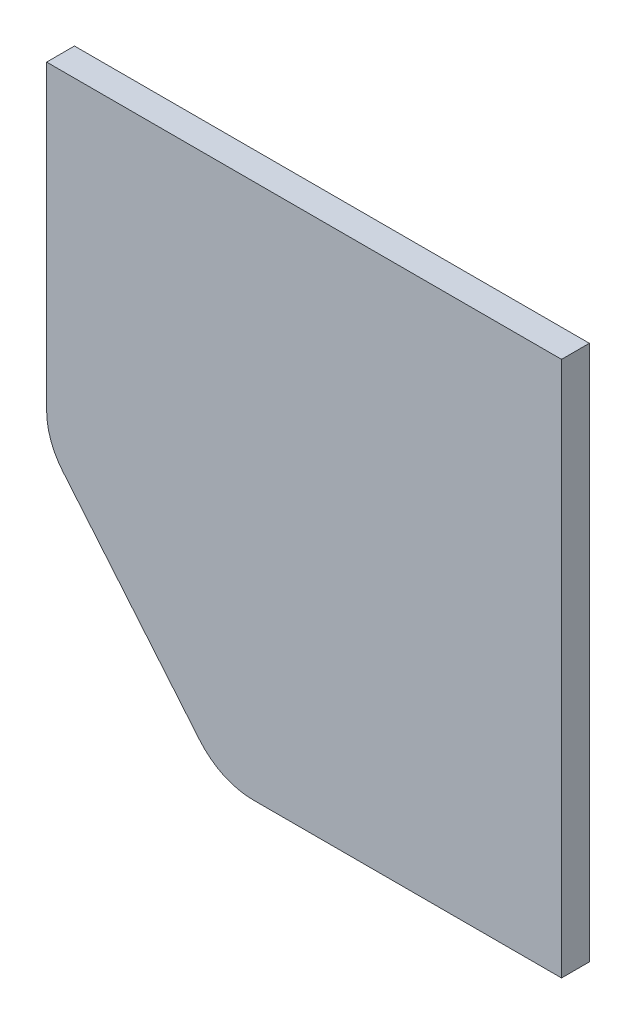
SolidWorks part; units mm, degrees
ref_plane "Plano frontal" through (0, 0, 0) normal (0, 0, 1) x (1, 0, 0)
ref_plane "Plano superior" through (0, 0, 0) normal (0, 1, 0) x (1, 0, 0)
ref_plane "Plano direito" through (0, 0, 0) normal (1, 0, 0) x (0, 0, -1)
sketch "Esboço1" plane through (0, 0, 0) normal (0, 0, 1) x (1, 0, 0)
  line L1 (-86.1657, 44.0263) -> (-12.1657, 44.0263)
  line L2 (-86.1657, 44.0263) -> (-86.1657, -32.9737)
  line L3 (-86.1657, -32.9737) -> (-12.1657, -32.9737)
  line L4 (-12.1657, 44.0263) -> (-12.1657, -32.9737)
  dimension "D1" = 77
  dimension "D2" = 74
extrude "Ressalto-extrusão1" add sketch "Esboço1" along normal blind 4
sketch "Esboço4" plane through (0, 0, 4) normal (0, 0, 1) x (1, 0, 0)
  line L0 (-61.1657, -32.9737) -> (-86.1657, -2.9737)
  line L1 (-86.1657, -32.9737) -> (-12.1657, -32.9737) construction
  line L2 (-86.1657, 44.0263) -> (-86.1657, -32.9737) construction
  dimension "D1" = 30
  dimension "D2" = 25
extrude "Corte-extrusão2" cut sketch "Esboço4" against normal through all and the other way through all
fillet "Filete2" radius 10 1 edges at (-86.1657, -2.9737, 2) type face fillet first side face at (-86.1657, 20.5263, 2) second side face at (-73.6657, -17.9737, 2)
fillet "Filete3" radius 10 1 edges at (-61.1657, -32.9737, 2) type face fillet first side face at (-72.5068, -19.3644, 2) second side face at (-36.6657, -32.9737, 2)
